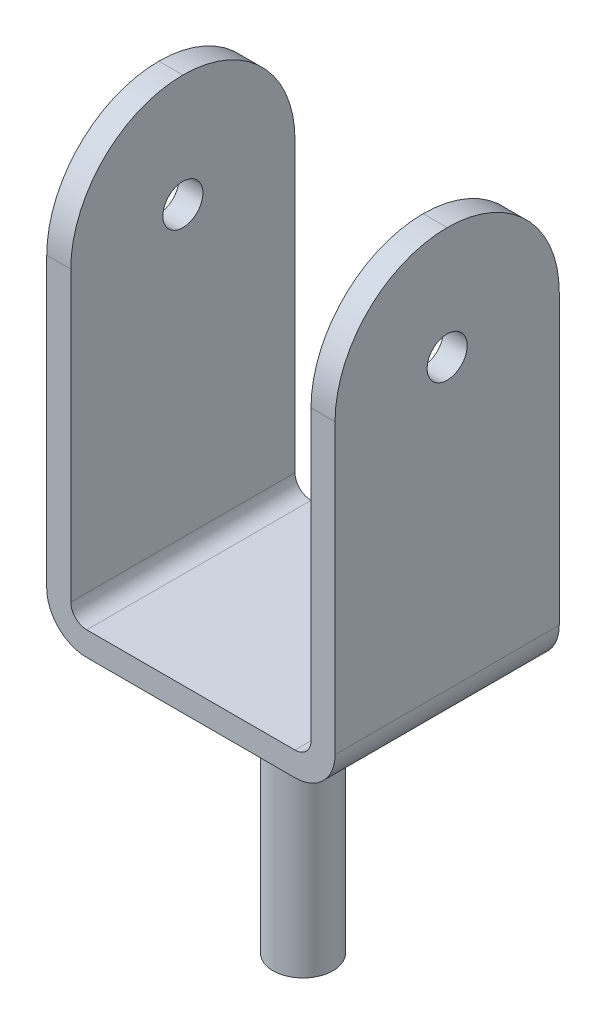
SolidWorks part; units mm, degrees
ref_plane "Front Plane" through (0, 0, 0) normal (0, 0, 1) x (1, 0, 0)
ref_plane "Top Plane" through (0, 0, 0) normal (0, 1, 0) x (1, 0, 0)
ref_plane "Right Plane" through (0, 0, 0) normal (1, 0, 0) x (0, 0, -1)
sketch "Sketch1" plane through (0, 0, 0) normal (0, 0, 1) x (1, 0, 0)
  line L0 (-150, 0) -> (150, 0)
  line L1 (-150, 0) -> (-150, 520)
  line L2 (0, 0) -> (0, 331.4118) construction
  line L3 (0, 0) -> (0, -51.1556) construction
  line L4 (-180, -30) -> (180, -30)
  line L5 (-180, -30) -> (-180, 520)
  line L6 (-150, 0) -> (180, 0) construction
  line L7 (-180, -30) -> (180, -30) construction
  line L8 (180, -30) -> (180, 520)
  line L9 (150, 0) -> (150, 520)
  line L10 (-180, 520) -> (-150, 520)
  line L11 (150, 520) -> (180, 520)
  point P13 (0, -30)
  dimension "D1" = 360
  dimension "D3" = 520
  dimension "D4" = 30
extrude "Boss-Extrude1" add sketch "Sketch1" along normal mid plane 280
fillet "Fillet1" radius 140 4 edges at (165, 520, 140) (165, 520, -140) (-165, 520, -140) (-165, 520, 140)
sketch "Sketch2" plane through (180, 0, 0) normal (1, 0, 0) x (0, 0, -1)
  circle A0 centre (0, 380) radius 25
  dimension "D1" = 50
extrude "Cut-Extrude1" cut sketch "Sketch2" against normal through all
sketch "Sketch3" plane through (0, -30, 0) normal (0, -1, 0) x (1, 0, 0)
  circle A0 centre (0, 0) radius 37.5
  dimension "D1" = 75
extrude "Boss-Extrude2" add sketch "Sketch3" along normal blind 325
fillet "Fillet2" radius 20 2 edges at (150, 0, 0) (-150, 0, 0)
fillet "Fillet3" radius 50 2 edges at (-180, -30, 0) (180, -30, 0)
